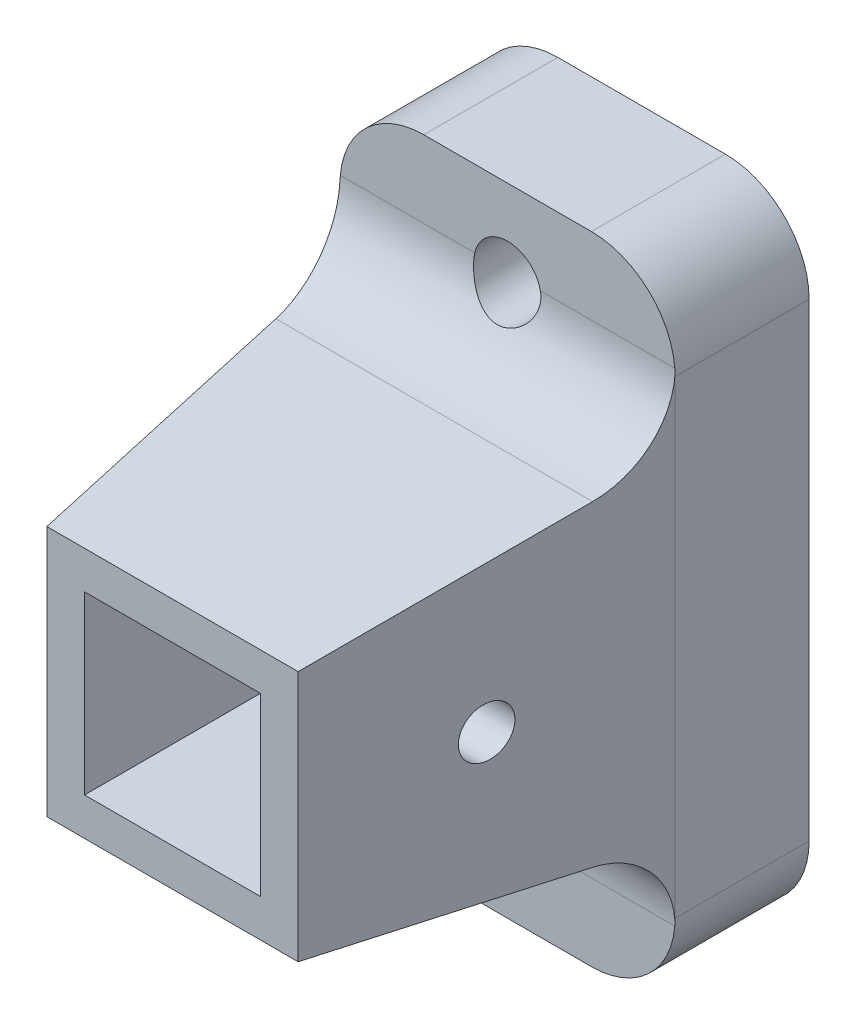
SolidWorks part; units mm, degrees
ref_plane "前视基准面" through (0, 0, 0) normal (0, 0, 1) x (1, 0, 0)
ref_plane "上视基准面" through (0, 0, 0) normal (0, 1, 0) x (1, 0, 0)
ref_plane "右视基准面" through (0, 0, 0) normal (1, 0, 0) x (0, 0, -1)
sketch "草图1" plane through (0, 0, 0) normal (0, 0, 1) x (1, 0, 0)
  line L1 (-10, 10) -> (10, 10)
  line L2 (-10, 10) -> (-10, -10)
  line L3 (-10, -10) -> (10, -10)
  line L4 (10, 10) -> (10, -10)
  line L5 (-10, 10) -> (10, -10) construction
  line L6 (-10, -10) -> (10, 10) construction
  point P0 (0, 0)
  dimension "D1" = 20
  dimension "D2" = 20
ref_plane "基准面2" through (0, 0, 20) normal (0, 0, 1) x (1, 0, 0)
sketch "草图7" plane through (0, 0, 20) normal (0, 0, 1) x (1, 0, 0)
  line L1 (-7.5, 7.5) -> (7.5, 7.5)
  line L2 (-7.5, 7.5) -> (-7.5, -7.5)
  line L3 (-7.5, -7.5) -> (7.5, -7.5)
  line L4 (7.5, 7.5) -> (7.5, -7.5)
  line L5 (-7.5, 7.5) -> (7.5, -7.5) construction
  line L6 (-7.5, -7.5) -> (7.5, 7.5) construction
  point P0 (0, 0)
  dimension "D1" = 15
  dimension "D2" = 15
loft "放样5" add profiles "草图7", "草图1" connector at (7.5, 7.5, 20) connector at (10, 10, 0)
sketch "草图8" plane through (0, 0, 20) normal (0, 0, 1) x (1, 0, 0)
  line L5 (-5.25, 5.25) -> (5.25, 5.25)
  line L6 (-5.25, 5.25) -> (-5.25, -5.25)
  line L7 (-5.25, -5.25) -> (5.25, -5.25)
  line L8 (5.25, 5.25) -> (5.25, -5.25)
  line L9 (-5.25, 5.25) -> (5.25, -5.25) construction
  line L10 (-5.25, -5.25) -> (5.25, 5.25) construction
  point P0 (0, 0)
  dimension "D1" = 10.5
  dimension "D2" = 10.5
extrude "切除-拉伸3" cut sketch "草图8" against normal blind 20
sketch "草图9" plane through (0, 0, 0) normal (1, 0, 0) x (0, 0, -1)
  line L0 (11.0001, 0) -> (-11.0001, 0) construction
  line L1 (-20, 11.0001) -> (-20, -11.0001) construction
  circle A0 centre (-10, 0) radius 1.5
  dimension "D1" = 3
  dimension "D2" = 10
extrude "切除-拉伸4" cut sketch "草图9" against normal blind 20 and the other way blind 20
sketch "草图10" plane through (0, 0, 0) normal (0, 0, -1) x (-1, 0, 0)
  line L1 (-10, 19) -> (10, 19)
  line L2 (-10, 19) -> (-10, -19)
  line L3 (-10, -19) -> (10, -19)
  line L4 (10, 19) -> (10, -19)
  line L5 (-10, 19) -> (10, -19) construction
  line L6 (-10, -19) -> (10, 19) construction
  point P0 (0, 0)
  dimension "D1" = 38
  dimension "D2" = 20
extrude "凸台-拉伸1" add sketch "草图10" along normal blind 8
sketch "草图11" plane through (0, 0, -8) normal (0, 0, -1) x (-1, 0, 0)
  line L0 (0, 11.0001) -> (0, -11.0001) construction
  line L1 (11.0001, 0) -> (-11.0001, 0) construction
  circle A0 centre (0, 14) radius 2
  circle A1 centre (0, -14) radius 2
  dimension "D1" = 4
  dimension "D2" = 14
extrude "切除-拉伸5" cut sketch "草图11" against normal blind 12
fillet "圆角1" radius 5 2 edges
ref_plane "基准面3" through (0, 0, -11) normal (0, 0, -1) x (-1, 0, 0)
fillet "圆角7" radius 5 4 edges at (10, -19, -4) (-10, -19, -4) (10, 19, -4) (-10, 19, -4)
